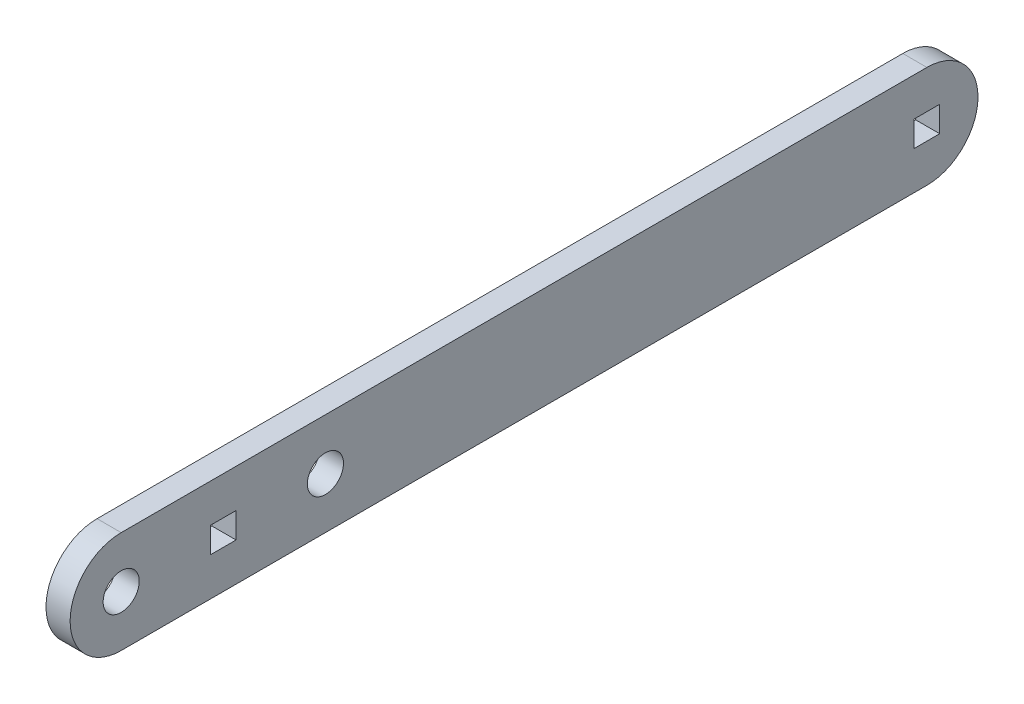
SolidWorks part; units mm, degrees
material "Custom Plastic"
ref_plane "Front Plane" through (0, 0, 0) normal (0, 0, 1) x (1, 0, 0)
ref_plane "Top Plane" through (0, 0, 0) normal (0, 1, 0) x (1, 0, 0)
ref_plane "Right Plane" through (0, 0, 0) normal (1, 0, 0) x (0, 0, -1)
sketch "Sketch1" plane through (0, 0, 0) normal (1, 0, 0) x (0, 0, -1)
  line L0 (0, 0) -> (-87.503, 0) construction
  line L1 (-101.7905, -1.5875) -> (-98.6155, 1.5875) construction
  line L2 (-85.9155, -1.5875) -> (-89.0905, -1.5875)
  line L3 (-85.9155, -1.5875) -> (-85.9155, 1.5875)
  line L4 (-85.9155, 1.5875) -> (-89.0905, 1.5875)
  line L5 (-89.0905, -1.5875) -> (-89.0905, 1.5875)
  line L6 (-85.9155, -1.5875) -> (-89.0905, 1.5875) construction
  line L7 (-85.9155, 1.5875) -> (-89.0905, -1.5875) construction
  line L8 (-76.3905, -1.5875) -> (-73.2155, 1.5875) construction
  line L9 (-100.203, 0) -> (-87.503, 0) construction
  line L10 (-100.203, 6.35) -> (0, 6.35)
  line L11 (-100.203, 6.35) -> (-100.203, 0) construction
  line L12 (0, -6.35) -> (-100.203, -6.35)
  line L13 (-100.203, 0) -> (-100.203, -6.35) construction
  line L20 (1.5875, -1.5875) -> (-1.5875, -1.5875)
  line L21 (1.5875, -1.5875) -> (1.5875, 1.5875)
  line L22 (1.5875, 1.5875) -> (-1.5875, 1.5875)
  line L23 (-1.5875, -1.5875) -> (-1.5875, 1.5875)
  line L24 (1.5875, -1.5875) -> (-1.5875, 1.5875) construction
  line L25 (1.5875, 1.5875) -> (-1.5875, -1.5875) construction
  circle A0 centre (-74.803, 0) radius 2.2451
  circle A1 centre (-100.203, 0) radius 2.2451
  circle A2 centre (0, 0) radius 2.2451 construction
  arc A3 (-100.203, 6.35) -> (-100.203, -6.35) centre (-100.203, 0) ccw
  arc A4 (0, 6.35) -> (0, -6.35) centre (0, 0) cw
  circle A9 centre (-87.503, 0) radius 2.2451 construction
  dimension "D5" = 6.35
  dimension "D1" = 87.503
  dimension "D2" = 3.175
  dimension "D3" = 12.7
  dimension "D4" = 12.7
extrude "Boss-Extrude1" add sketch "Sketch1" along normal blind 3
